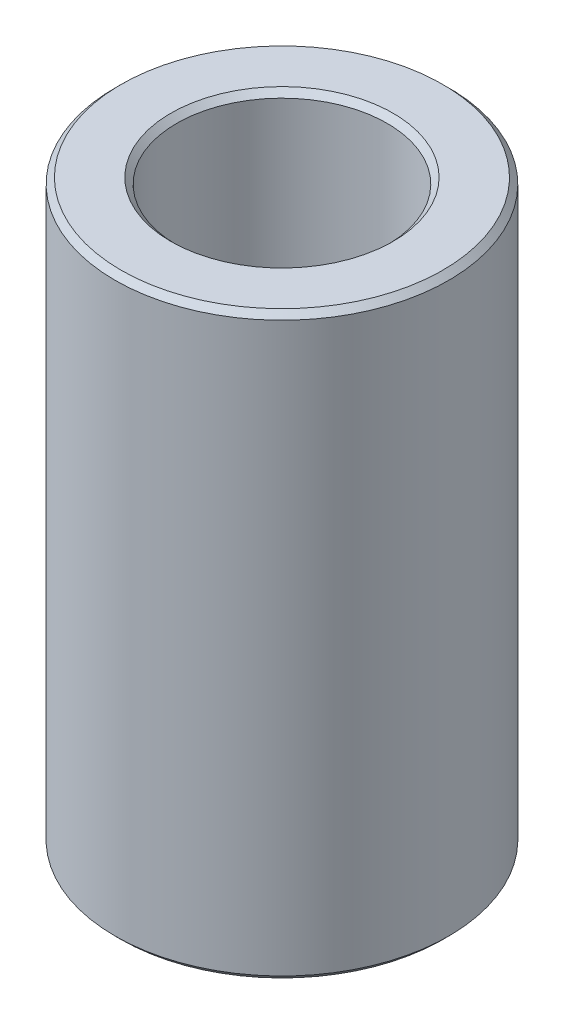
SolidWorks part; units mm, degrees
ref_plane "Front Plane" through (0, 0, 0) normal (0, 0, 1) x (1, 0, 0)
ref_plane "Top Plane" through (0, 0, 0) normal (0, 1, 0) x (1, 0, 0)
ref_plane "Right Plane" through (0, 0, 0) normal (1, 0, 0) x (0, 0, -1)
sketch "Sketch1" plane through (0, 0, 0) normal (0, 1, 0) x (1, 0, 0)
  circle A0 centre (0, 0) radius 30
  dimension "SLEEVE_OD" = 60
extrude "Boss-Extrude1" add sketch "Sketch1" along normal blind 104.2664
sketch "Sketch2" plane through (0, 0, 0) normal (0, 1, 0) x (1, 0, 0)
  circle A0 centre (0, 0) radius 18.9355
  dimension "BORE_D" = 37.871
extrude "Cut-Extrude1" cut sketch "Sketch2" along normal through all
chamfer "Chamfer1" distance 1.0554 angle 45 4 edges at (0, 104.2664, 18.9355) (0, 0, 18.9355) (0, 0, 30) (0, 104.2664, 30)
